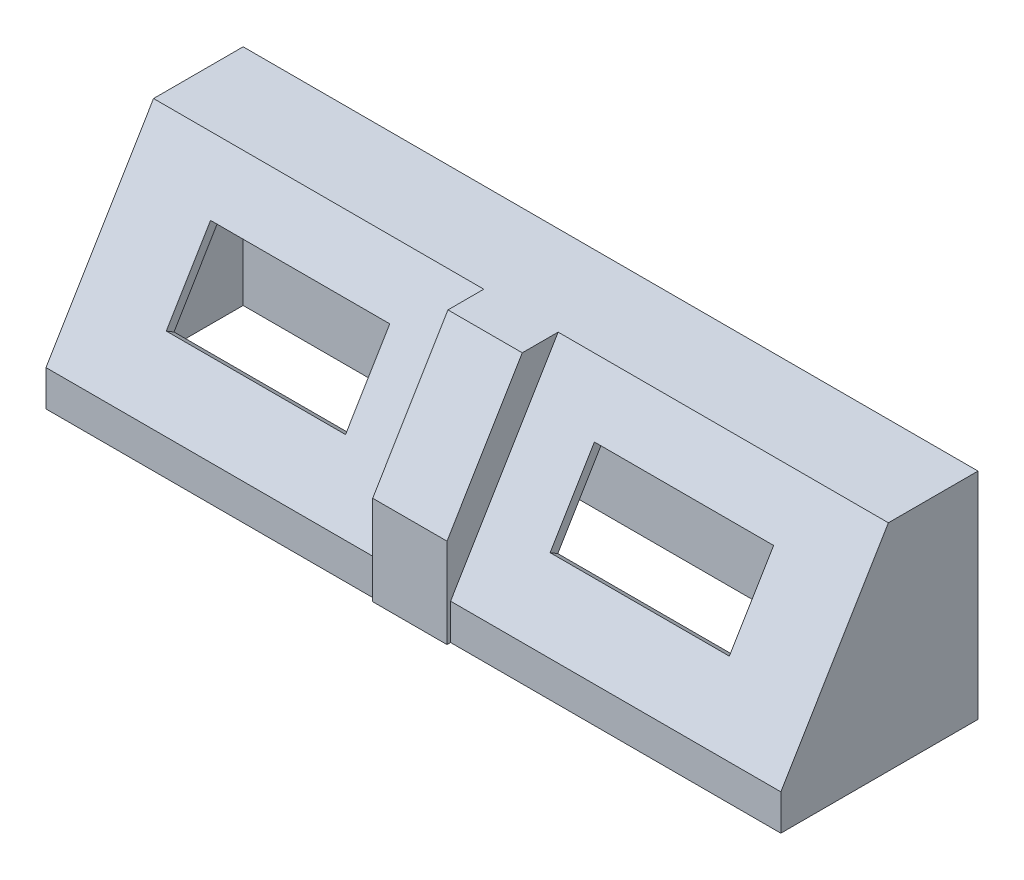
SolidWorks part; units mm, degrees
ref_plane "Front" through (0, 0, 0) normal (0, 0, 1) x (1, 0, 0)
ref_plane "Top" through (0, 0, 0) normal (0, 1, 0) x (1, 0, 0)
ref_plane "Right" through (0, 0, 0) normal (1, 0, 0) x (0, 0, -1)
sketch "Sketch1" plane through (0, 0, 0) normal (1, 0, 0) x (0, 0, -1)
  line L0 (0, 0) -> (0, 76.2)
  line L1 (0, 55) -> (0, -55) construction
  line L2 (0, 76.2) -> (-31.75, 76.2)
  line L3 (-31.75, 76.2) -> (-69.85, 12.7)
  line L4 (-69.85, 12.7) -> (-69.85, 0)
  line L5 (55, 0) -> (-55, 0) construction
  line L6 (-69.85, 0) -> (0, 0)
  line L7 (-66.675, 0) -> (-66.675, 11.8206)
  line L8 (-66.675, 11.8206) -> (-29.9523, 73.025)
  line L9 (-29.9523, 73.025) -> (-3.175, 73.025)
  line L10 (-3.175, 73.025) -> (-3.175, 0)
  dimension "D1" = 31.75
  dimension "D2" = 76.2
  dimension "D3" = 12.7
  dimension "D4" = 3.175
  dimension "D5" = 3.175
  dimension "D6" = 3.175
  dimension "D7" = 3.175
  dimension "D8" = 69.85
extrude "Boss-Extrude1" add sketch "Sketch1" along normal mid plane 254 contours L9 L10 L6 L0 L2 L3 L4 L7 L8 region at (0, 1.0337, 1.5875)
sketch "Sketch2" plane through (127, 0, 0) normal (1, 0, 0) x (0, 0, -1)
  line L0 (-66.675, 0) -> (-3.175, 0)
  line L10 (-29.9523, 73.025) -> (-3.175, 73.025)
  line L11 (-3.175, 73.025) -> (-3.175, 0)
  line L12 (-3.175, 0) -> (0, 0)
  line L13 (0, 0) -> (0, 76.2)
  line L14 (0, 76.2) -> (-31.75, 76.2)
  line L15 (-31.75, 76.2) -> (-69.85, 12.7)
  line L16 (-69.85, 12.7) -> (-69.85, 0)
  line L17 (-69.85, 0) -> (-66.675, 0)
  line L18 (-66.675, 0) -> (-66.675, 11.8206)
  line L19 (-66.675, 11.8206) -> (-29.9523, 73.025)
  line L20 (-29.9523, 73.025) -> (-3.175, 73.025)
  line L21 (-3.175, 73.025) -> (-3.175, 0)
  line L22 (-3.175, 0) -> (0, 0)
  line L23 (0, 0) -> (0, 76.2)
  line L24 (0, 76.2) -> (-31.75, 76.2)
  line L25 (-31.75, 76.2) -> (-69.85, 12.7)
  line L26 (-69.85, 12.7) -> (-69.85, 0)
  line L27 (-69.85, 0) -> (-66.675, 0)
  line L28 (-66.675, 0) -> (-66.675, 11.8206)
  line L29 (-66.675, 11.8206) -> (-29.9523, 73.025)
  line M11 (-29.9523, 73.025) -> (-3.175, 73.025)
  line M12 (-3.175, 73.025) -> (-3.175, 0)
  line M13 (-3.175, 0) -> (0, 0)
  line M14 (0, 0) -> (0, 76.2)
  line M15 (0, 76.2) -> (-31.75, 76.2)
  line M16 (-31.75, 76.2) -> (-69.85, 12.7)
  line M17 (-69.85, 12.7) -> (-69.85, 0)
  line M18 (-69.85, 0) -> (-66.675, 0)
  line M19 (-66.675, 0) -> (-66.675, 11.8206)
  line M20 (-66.675, 11.8206) -> (-29.9523, 73.025)
  dimension "D1" = 0
extrude "Boss-Extrude2" add sketch "Sketch2" along normal blind 3.175 contours L0 M19 M12 M11 M20 | M20 M11 M12 M13 M14 M15 M16 M17 M18 M19 region at (127, 31.3591, 28.6846) region at (127, 1.0337, 68.2625)
mirror "Mirror1" about plane through (0, 0, 0) normal (1, 0, 0) of "Boss-Extrude2"
sketch "Sketch3" plane through (0, 34.1779, 56.9632) normal (0, 0.5145, 0.8575) x (1, 0, 0)
  line L0 (0, -38.4175) -> (0, 38.4175) construction
  line L1 (-99.7435, 29.1199) -> (-36.2435, 29.1199)
  line L2 (-99.7435, 29.1199) -> (-99.7435, -1.3601)
  line L3 (-99.7435, -1.3601) -> (-36.2435, -1.3601)
  line L4 (-36.2435, 29.1199) -> (-36.2435, -1.3601)
  line L5 (-99.7435, 29.1199) -> (-36.2435, -1.3601) construction
  line L6 (-99.7435, -1.3601) -> (-36.2435, 29.1199) construction
  line L7 (99.7435, -1.3601) -> (36.2435, -1.3601)
  line L8 (36.2435, 29.1199) -> (36.2435, -1.3601)
  line L9 (99.7435, 29.1199) -> (36.2435, 29.1199)
  line L10 (99.7435, 29.1199) -> (99.7435, -1.3601)
  point P0 (-67.9935, 13.8799)
  dimension "D1" = 63.5
  dimension "D2" = 30.48
extrude "Cut-Extrude1" cut sketch "Sketch3" against normal up to surface (3.175 mm away) up to face at (0, 42.4228, 48.3137)
sketch "Sketch5" plane through (0, 0, 0) normal (0, 0, 1) x (1, 0, 0)
  line L0 (130.175, 76.2) -> (-130.175, 76.2) construction
  line L1 (-13.1679, 76.2) -> (13.1679, 76.2)
  line L2 (-13.1679, 76.2) -> (-13.1679, 31.75)
  line L3 (-13.1679, 31.75) -> (13.1679, 31.75)
  line L4 (13.1679, 76.2) -> (13.1679, 31.75)
  line L5 (0, -38.4175) -> (0, 38.4175) construction
  point P6 (0, 31.75)
  dimension "D1" = 44.45
extrude "Boss-Extrude3" add sketch "Sketch5" along normal blind 12.7 from surface starting at face at (-67.9935, 46.0799, 49.8221)
sketch "Sketch10" plane through (0, 31.75, 0) normal (0, -1, 0) x (1, 0, 0)
  line L1 (-13.1679, 71.12) -> (13.1679, 71.12)
  line L2 (-13.1679, 71.12) -> (-13.1679, 58.42)
  line L3 (-13.1679, 58.42) -> (13.1679, 58.42)
  line L4 (13.1679, 71.12) -> (13.1679, 58.42)
extrude "Boss-Extrude5" add sketch "Sketch10" along normal up to surface (31.75 mm away) up to plane "Top"
sketch "Sketch11" plane through (0, 0, 3.175) normal (0, 0, 1) x (1, 0, 0)
  line L0 (-13.1679, 31.75) -> (13.1679, 31.75) construction
  line L1 (-10.6279, 73.66) -> (10.6279, 73.66)
  line L2 (-10.6279, 73.66) -> (-10.6279, 31.75)
  line L3 (-10.6279, 31.75) -> (10.6279, 31.75)
  line L4 (10.6279, 73.66) -> (10.6279, 31.75)
  line L5 (13.1679, 76.2) -> (-13.1679, 76.2) construction
  line L6 (-13.1679, 76.2) -> (-13.1679, 31.75) construction
  line L7 (0, -39.116) -> (0, 39.116) construction
  line L8 (39.116, 0) -> (-39.116, 0) construction
  line L9 (-10.6279, 31.75) -> (10.6279, 31.75)
  line L10 (-10.6279, 31.75) -> (-10.6279, 0)
  line L11 (-10.6279, 0) -> (10.6279, 0)
  line L12 (10.6279, 31.75) -> (10.6279, 0)
  point P10 (0, 73.66)
  line M6 (127, 73.025) -> (-127, 73.025)
  dimension "D1" = 2.54
  dimension "D2" = 2.54
extrude "Cut-Extrude7" cut sketch "Sketch11" along normal blind 12.7 from surface contours L4 L2 L3 M6 region at (0, 52.3875, 3.175) starting at face at (67.9935, 44.4464, 47.0995)
sketch "Sketch12" plane through (0, 0, 71.12) normal (0, 0, 1) x (1, 0, 0)
  line L0 (-13.1679, 31.75) -> (13.1679, 31.75) construction
  line L1 (-10.6279, 31.75) -> (10.6279, 31.75)
  line L2 (-10.6279, 31.75) -> (-10.6279, 0)
  line L3 (-10.6279, 0) -> (10.6279, 0)
  line L4 (10.6279, 31.75) -> (10.6279, 0)
  line L5 (39.116, 0) -> (-39.116, 0) construction
  line L6 (-10.6279, 31.75) -> (-10.6279, 0) construction
  line L8 (0, -39.116) -> (0, 39.116) construction
  point P12 (0, 31.75)
extrude "Cut-Extrude8" cut sketch "Sketch12" against normal blind 15.24 from offset 2.54 offset against normal yes
sketch "Sketch13" plane through (13.1679, 0, 0) normal (1, 0, 0) x (0, 0, -1)
  line L4 (-58.42, 25.5789) -> (-66.675, 11.8206)
  line L5 (-66.675, 11.8206) -> (-66.675, 0)
  line L6 (-66.675, 0) -> (-58.42, 0)
  line L7 (-58.42, 0) -> (-58.42, 25.5789)
  line L8 (-58.42, 25.5789) -> (-66.675, 11.8206)
  line L9 (-66.675, 11.8206) -> (-66.675, 0)
  line L10 (-66.675, 0) -> (-58.42, 0)
  line L11 (-58.42, 0) -> (-58.42, 25.5789)
  dimension "D1" = 0
extrude "Cut-Extrude9" cut sketch "Sketch13" against normal up to vertex (26.3359 mm away) up to point (-13.1679, 0, 58.42)
